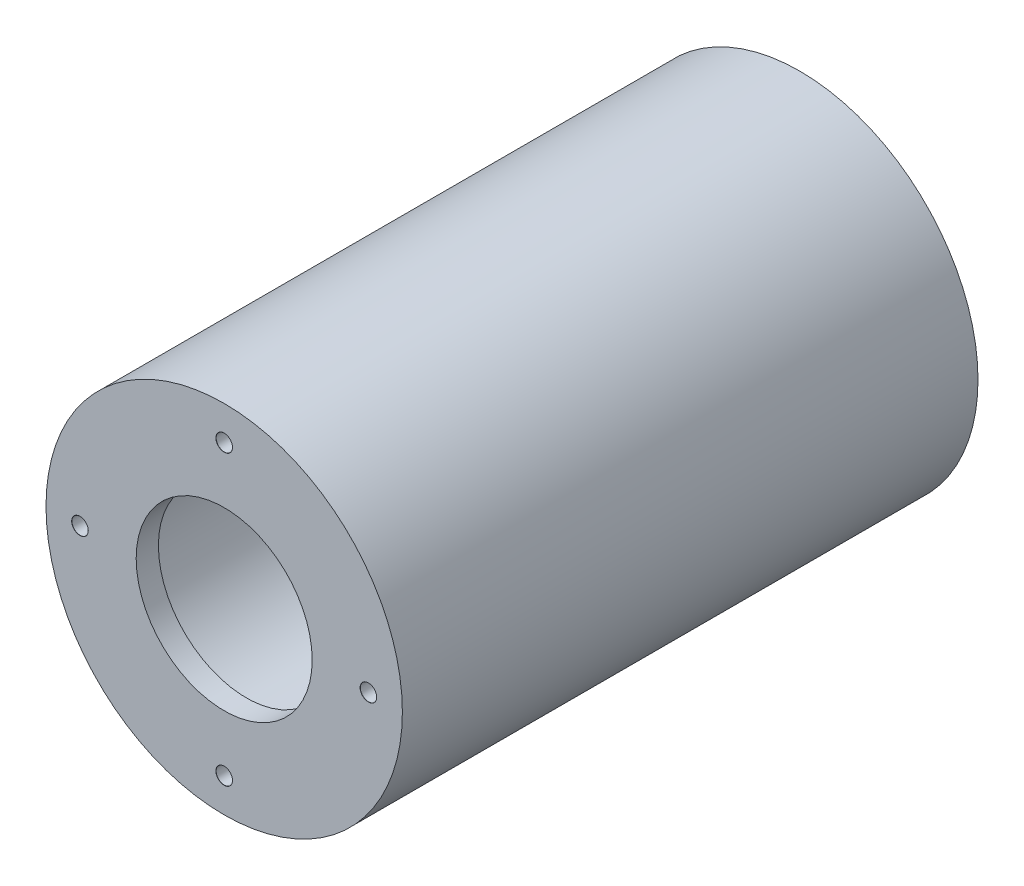
SolidWorks part; units mm, degrees
material "6061-T6 (SS)"
ref_plane "Front Plane" through (0, 0, 0) normal (0, 0, 1) x (1, 0, 0)
ref_plane "Top Plane" through (0, 0, 0) normal (0, 1, 0) x (1, 0, 0)
ref_plane "Right Plane" through (0, 0, 0) normal (1, 0, 0) x (0, 0, -1)
sketch "Sketch Spindle Skeleton" plane through (0, 0, 0) normal (1, 0, 0) x (0, 0, -1)
  line L0 (-119.9, -9.5) -> (-144, -9.5)
  line L5 (-1000, 0) -> (49000, 0)
  line L6 (0, -9.5) -> (0, 9.5)
  line L13 (0, 9.5) -> (-48.3, 9.5)
  line L26 (-48.3, 9.5) -> (-48.3, 14)
  line L27 (-48.3, 14) -> (-119.9, 14)
  line L32 (-119.9, 14) -> (-119.9, 9.5)
  line L34 (-160, 7) -> (-160, -7)
  line L36 (-119.9, -9.5) -> (-119.9, -14)
  line L37 (-119.9, -14) -> (-48.3, -14)
  line L38 (-48.3, -14) -> (-48.3, -9.5)
  line L39 (0, -9.5) -> (-48.3, -9.5)
  line L40 (-24.2, 36) -> (-19.2, 36)
  line L41 (-136.5, 22.5) -> (-119.9, 22.5)
  line L42 (-136.5, 22.5) -> (-136.5, -22.5)
  line L43 (-136.5, -22.5) -> (-119.9, -22.5)
  line L44 (-119.9, 22.5) -> (-119.9, -22.5)
  line L45 (-136.5, 22.5) -> (-119.9, -22.5) construction
  line L46 (-136.5, -22.5) -> (-119.9, 22.5) construction
  line L47 (-31.7, 22.5) -> (-48.3, 22.5)
  line L48 (-31.7, 22.5) -> (-31.7, -22.5)
  line L49 (-31.7, -22.5) -> (-48.3, -22.5)
  line L50 (-48.3, 22.5) -> (-48.3, -22.5)
  line L51 (-31.7, 22.5) -> (-48.3, -22.5) construction
  line L52 (-31.7, -22.5) -> (-48.3, 22.5) construction
  line L59 (-19.2, 36) -> (-19.2, -36)
  line L60 (-19.2, -36) -> (-24.2, -36)
  line L61 (-24.2, -22.5) -> (-29.2, -22.5)
  line L62 (-29.2, -22.5) -> (-29.2, -17.5)
  line L63 (-29.2, -17.5) -> (-24.2, -17.5)
  line L64 (-24.2, -17.5) -> (-24.2, 17.5)
  line L65 (-24.2, 17.5) -> (-29.2, 17.5)
  line L66 (-29.2, 17.5) -> (-29.2, 22.5)
  line L67 (-29.2, 22.5) -> (-24.2, 22.5)
  line L68 (-24.2, 22.5) -> (-24.2, 36)
  line L69 (-24.2, -22.5) -> (-24.2, -36)
  line L71 (-141.5, 36) -> (-25.2, 36)
  line L72 (-141.5, 36) -> (-141.5, -36)
  line L73 (-141.5, -36) -> (-25.2, -36)
  line L74 (-25.2, 36) -> (-25.2, -36)
  line L75 (-141.5, 36) -> (-25.2, -36) construction
  line L76 (-141.5, -36) -> (-25.2, 36) construction
  line L77 (-144, -9.5) -> (-144, -7)
  line L78 (-144, -7) -> (-160, -7)
  line L79 (-119.9, 9.5) -> (-144, 9.5)
  line L80 (-144, 7) -> (-160, 7)
  line L81 (-144, 9.5) -> (-144, 7)
  line L82 (-131.95, 9.5) -> (-131.95, -9.5) construction
  line L83 (-24.15, 9.5) -> (-24.15, -9.5) construction
  point P3 (0, 0)
  point P18 (-128.2, 0)
  point P24 (-40, 0)
  point P29 (-83.35, 0)
  point P48 (-19.2, 29.25)
sketch "Sketch1" plane through (0, 0, 0) normal (1, 0, 0) x (0, 0, -1)
  line L0 (-25.2, 36) -> (-25.2, -36) construction
  line L1 (-141.5, -36) -> (-25.2, -36) construction
  line L2 (-141.5, 36) -> (-141.5, -36) construction
  line L3 (-141.5, 36) -> (-25.2, 36) construction
  line L4 (-25.2, 36) -> (-25.2, -36)
  line L5 (-141.5, -36) -> (-25.2, -36)
  line L6 (-141.5, 36) -> (-141.5, -36)
  line L7 (-141.5, 36) -> (-25.2, 36)
  line L8 (-141.5, 17.78) -> (-137.008, 17.78)
  line L9 (-137.008, 17.78) -> (-137.008, 22.5)
  line L10 (-137.008, 22.5) -> (-25.2, 22.5)
  line L12 (-136.5, 22.5) -> (-136.5, -22.5) construction
  line L13 (-136.5, 22.5) -> (-119.9, 22.5) construction
  line L14 (-201000, 0) -> (249000, 0) construction
  line L15 (-141.5, 0) -> (-25.2, 0) construction
  dimension "D1" = 0.508
  dimension "D2" = 0
  dimension "D3" = 17.78
revolve "Revolve1" add sketch "Sketch1" angle 360 about L15 region at (0, 29.1286, 84.0949)
sketch "Sketch2" plane through (0, 0, 25.2) normal (0, 0, -1) x (-1, 0, 0)
  circle A0 centre (0, 0) radius 29.1369 construction
  point P3 (0, 29.1369)
  point P4 (29.1369, 0)
  point P5 (0, -29.1369)
  point P6 (-29.1369, 0)
hole_wizard "Tap Drill for M4x0.7 Tap1" positions "Sketch5" profile "Sketch6" hole size "M4x0.7" standard "ANSI Metric"
sketch "Sketch5" plane through (0, 0, 25.2) normal (0, 0, -1) x (-1, 0, 0)
  point P0 (0, 29.1369)
  point P3 (29.1369, 0)
  point P6 (0, -29.1369)
  point P9 (-29.1369, 0)
sketch "Sketch6" plane through (0, 29.1369, 25.2) normal (1, 0, 0) x (0, 1, 0)
  line L0 (0, 0) -> (0, 10.9914)
  line L1 (0, 10.9914) -> (1.65, 10)
  line L2 (1.65, 10) -> (1.65, 0.025)
  line L3 (1.65, 0.025) -> (1.675, 0)
  line L5 (1.675, 0) -> (0, 0)
  line L6 (-1.65, 0.025) -> (-1.675, 0) construction
  line L10 (0, 10.9914) -> (-1.65, 10) construction
  line L11 (0, -6.35) -> (0, 107.95) construction
  dimension "Hole Dia." = 3.3
  dimension "Hole Depth" = 10
  dimension "Near C'Sink Dia." = 3.35
  dimension "Near C'Sink Angle" = 90
  dimension "Drill Angle" = 118
ref_plane "Plane1" through (0, 0, 83.35) normal (0, 0, -1) x (-1, 0, 0)
mirror "Mirror1" about plane through (0, 0, 83.35) normal (0, 0, -1) of "Tap Drill for M4x0.7 Tap1"
equation "\"D2@Sketch1\"=15*10^(-6)"
